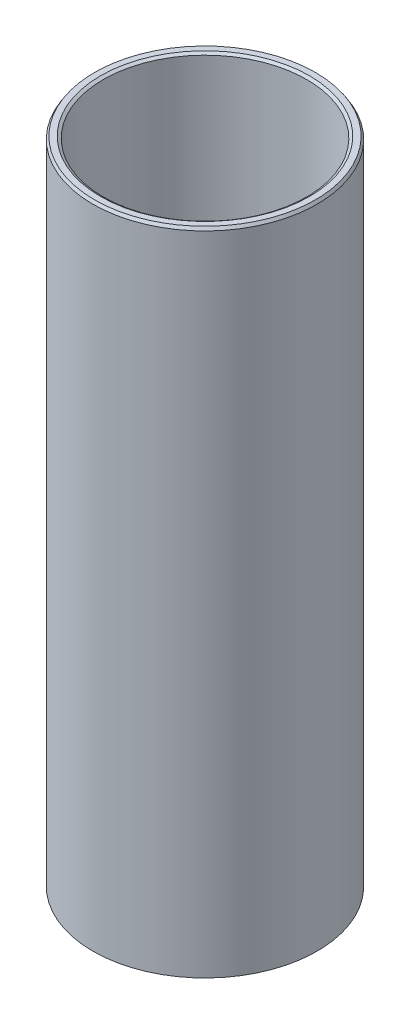
SolidWorks part; units mm, degrees
ref_plane "Front Plane" through (0, 0, 0) normal (0, 0, 1) x (1, 0, 0)
ref_plane "Top Plane" through (0, 0, 0) normal (0, 1, 0) x (1, 0, 0)
ref_plane "Right Plane" through (0, 0, 0) normal (1, 0, 0) x (0, 0, -1)
sketch "Sketch1" plane through (0, 0, 0) normal (0, 1, 0) x (1, 0, 0)
  circle A0 centre (0, 0) radius 55
  dimension "SLEEVE_OD" = 110
extrude "Boss-Extrude1" add sketch "Sketch1" along normal blind 319.3195
sketch "Sketch2" plane through (0, 0, 0) normal (0, 1, 0) x (1, 0, 0)
  circle A0 centre (0, 0) radius 49.8555
  dimension "BORE_D" = 99.711
extrude "Cut-Extrude1" cut sketch "Sketch2" along normal through all
chamfer "Chamfer1" distance 1.3747 angle 32.974 4 edges at (0, 319.3195, 49.8555) (0, 0, 49.8555) (0, 0, 55) (0, 319.3195, 55) first distance on face at (0, 319.3195, 49.8555) first distance on face at (0, 0, 49.8555) first distance on face at (0, 319.3195, 55)
